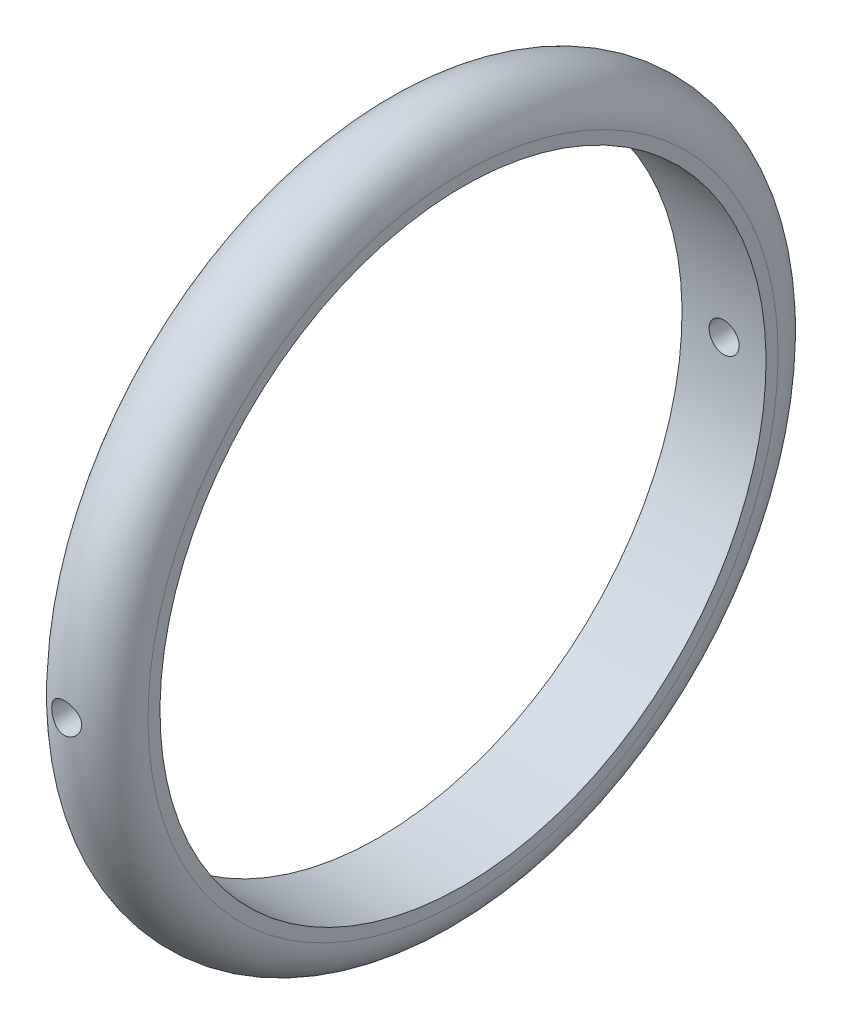
SolidWorks part; units mm, degrees
note: The reader was unsure of these and kept them because the rebuilt part matched: shared geometry of "Sketch1<3>".
ref_plane "Front Plane" through (0, 0, 0) normal (0, 0, 1) x (1, 0, 0)
ref_plane "Top Plane" through (0, 0, 0) normal (0, 1, 0) x (1, 0, 0)
ref_plane "Right Plane" through (0, 0, 0) normal (1, 0, 0) x (0, 0, -1)
sketch "Sketch1" plane through (0, 0, 0) normal (0, 0, 1) x (1, 0, 0)
  line L1 (0, 0) -> (14, 0) construction
  line L2 (0, 0) -> (0, 52.5) construction
  line L3 (0, 52.5) -> (14, 52.5)
  line L4 (14, 0) -> (14, 52.5) construction
  line L5 (0, 52.5) -> (14, 52.5)
  line L6 (0, 52.5) -> (0, 50.5)
  line L7 (0, 50.5) -> (14, 50.5)
  line L8 (14, 52.5) -> (14, 50.5)
  arc A0 (0, 52.5) -> (14, 52.5) centre (7, 52.5) cw
  circle A1 centre (7, 0) radius 2.5
  dimension "D4" = 5
  dimension "D1" = 52.5
  dimension "D2" = 14
  dimension "D3" = 2
revolve "Revolve1" add sketch "Sketch1" angle 360 about L1
extrude "Cut-Extrude1" cut sketch "Sketch1<3>" against normal up to surface and the other way up to surface contours A1
sketch "Sketch1<3>" plane through (0, 0, 0) normal (0, 0, 1) x (1, 0, 0) same geometry as "Sketch1"
